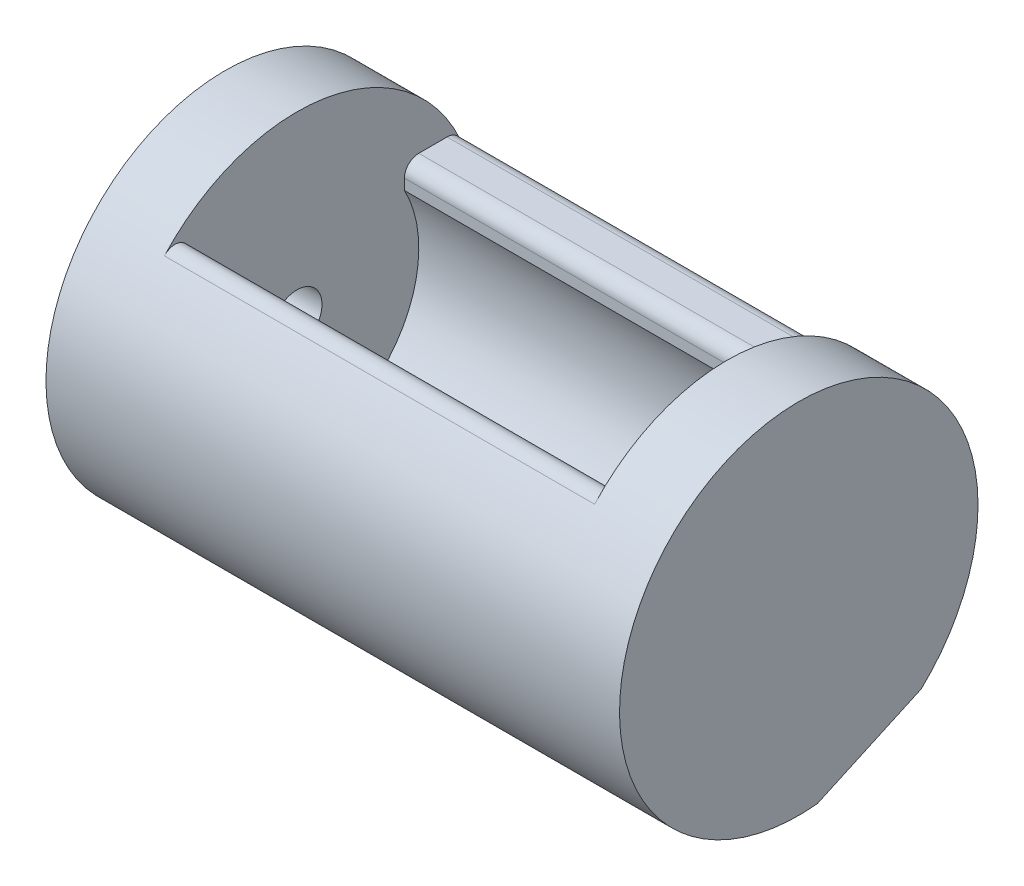
SolidWorks part; units mm, degrees
ref_plane "Front Plane" through (0, 0, 0) normal (0, 0, 1) x (1, 0, 0)
ref_plane "Top Plane" through (0, 0, 0) normal (0, 1, 0) x (1, 0, 0)
ref_plane "Right Plane" through (0, 0, 0) normal (1, 0, 0) x (0, 0, -1)
sketch "Sketch2" plane through (0, 0, 0) normal (1, 0, 0) x (0, 0, -1)
  circle A0 centre (0, 0) radius 25
extrude "Boss-Extrude1" add sketch "Sketch2" along normal blind 80 contours A0
sketch "Sketch4" plane through (0, 0, 0) normal (0, 1, 0) x (1, 0, 0)
  line L0 (10, 0) -> (10, 15)
  line L2 (10, 15) -> (70, 15)
  line L3 (10, 0) -> (10, -15)
  line L4 (10, -15) -> (70, -15)
  line L5 (70, -15) -> (70, 15)
  dimension "D1" = 10
  dimension "D2" = 60
  dimension "D3" = 15
  dimension "D4" = 30
extrude "Cut-Extrude3" cut sketch "Sketch4" along normal blind 30 contours L0 L2 L5 L4 L3
ref_plane "Plane1" through (30, 0, 0) normal (1, 0, 0) x (0, 0, -1)
sketch "Sketch5" plane through (30, 0, 0) normal (1, 0, 0) x (0, 0, -1)
  circle A0 centre (0, 0) radius 17
extrude "Cut-Extrude4" cut sketch "Sketch5" against normal blind 20 and the other way blind 40
fillet "Fillet3" radius 2 2 edges at (40, 20, 15) (40, 20, -15)
sketch "Sketch6" plane through (0, 0, 0) normal (1, 0, 0) x (0, 0, -1)
  circle A0 centre (0, 0) radius 3.5
  point P4 (0, 0)
  point P8 (8.5, 0)
extrude "Cut-Extrude5" cut sketch "Sketch6" along normal blind 20
sketch "Sketch7" plane through (0, 0, 0) normal (1, 0, 0) x (0, 0, -1)
  line L1 (-8.5, -0.45) -> (-8.5, 0)
  line L2 (8.5, 0) -> (8.5, -17.5)
  line L3 (8.5, -17.5) -> (-8.5, -17.5)
  line L4 (-8.5, -17.5) -> (-8.5, -0.45)
  arc A0 (-8.5, 0) -> (8.5, 0) centre (0, 0) cw
  point P5 (0, 0)
extrude "Cut-Extrude7" cut sketch "Sketch7" along normal blind 3 contours L2 L3 L4 L1 A0
sketch "Sketch9" plane through (0, 0, 0) normal (0, 0, 1) x (1, 0, 0)
  line L12 (10, 17.4919) -> (70, 17.4919)
  line L13 (70, 25) -> (70, 16.8391) construction
  line L14 (70, 17.4919) -> (10, 17.4919) construction
  line L15 (70, 17.4919) -> (70, 11.4919)
  line L16 (70, 11.4919) -> (10, 11.4919)
  line L17 (10, 11.4919) -> (10, 17.4919)
extrude "Cut-Extrude9" cut sketch "Sketch9" against normal blind 30
fillet "Fillet5" radius 2 2 edges at (40, 11.4919, -15) (40, 11.4919, -22.2022)
sketch "Sketch10" plane through (0, 0, 0) normal (1, 0, 0) x (0, 0, -1)
  line L4 (2.5964, -24.8648) -> (17.0817, -18.2542)
  line L5 (17.0817, -18.2542) -> (17.8078, -19.8451)
  line L6 (17.8078, -19.8451) -> (3.3224, -26.4557)
  line L7 (3.3224, -26.4557) -> (2.5964, -24.8648)
  circle A1 centre (0, 0) radius 25 construction
extrude "Cut-Extrude10" cut sketch "Sketch10" along normal through all
sketch "Sketch11" plane through (0, 0, 0) normal (1, 0, 0) x (0, 0, -1)
  line L0 (8.5, -17.5) -> (-8.5, -17.5)
  line L1 (-8.5, -17.5) -> (-8.5, -18.75)
  line L2 (-8.5, -18.75) -> (9.75, -18.75)
  line L3 (9.75, -18.75) -> (9.75, 0)
  line L4 (9.75, 0) -> (8.5, 0)
  line L5 (8.5, 0) -> (8.5, -17.5)
  dimension "D1" = 1.25
  dimension "D2" = 1.25
extrude "Boss-Extrude2" add sketch "Sketch11" against normal blind 2.5
